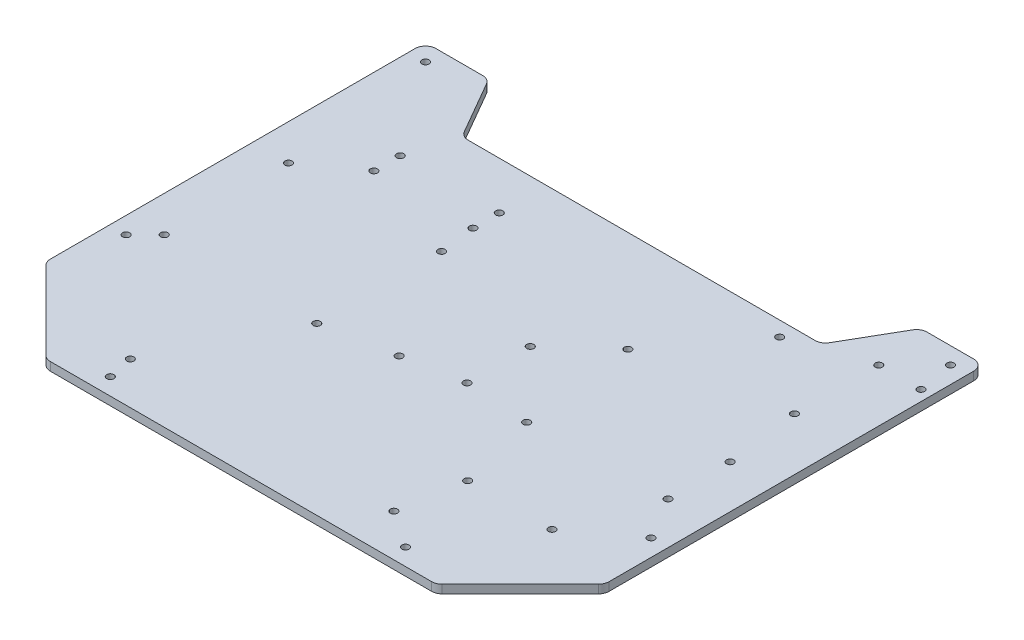
SolidWorks part; units mm, degrees
material "Acier non allié"
ref_plane "Front" through (0, 0, 0) normal (0, 0, 1) x (1, 0, 0)
ref_plane "Top" through (0, 0, 0) normal (0, 1, 0) x (1, 0, 0)
ref_plane "Right" through (0, 0, 0) normal (1, 0, 0) x (0, 0, -1)
sketch "Main scetch" plane through (0, 0, 0) normal (0, 1, 0) x (1, 0, 0)
  line L1 (0, 0) -> (132.5, 0) construction
  line L2 (0, 0) -> (0, 220) construction
  line L3 (0, 220) -> (132.5, 220) construction
  line L4 (132.5, 0) -> (132.5, 220) construction
  line L13 (-92.5, 0) -> (92.5, 0)
  line L14 (92.5, 0) -> (132.5, 40)
  line L15 (132.5, 40) -> (132.5, 220)
  line L16 (132.5, 220) -> (102.5, 220)
  line L17 (102.5, 220) -> (85.1795, 190)
  line L18 (85.1795, 190) -> (-85.1795, 190)
  line L19 (-102.5, 220) -> (-85.1795, 190)
  line L20 (-132.5, 220) -> (-102.5, 220)
  line L21 (-132.5, 40) -> (-132.5, 220)
  line L22 (-92.5, 0) -> (-132.5, 40)
  point P11 (0, 190)
  dimension "132.5" = 132.5
  dimension "D2" = 220
  dimension "D1" = 40
  dimension "D3" = 40
  dimension "D4" = 30
  dimension "D5" = 60
  dimension "D6" = 30
extrude "Main extrusion" add sketch "Main scetch" along normal blind 4
fillet "Congé1" radius 5 10 edges at (-132.5, 2, -40) (-92.5, 2, 0) (92.5, 2, 0) (132.5, 2, -40) (132.5, 2, -220) (102.5, 2, -220) (85.1795, 2, -190) (-85.1795, 2, -190) (-102.5, 2, -220) (-132.5, 2, -220)
sketch "Esquisse1" plane through (0, 4, 0) normal (0, 1, 0) x (1, 0, 0)
  line L0 (0, 0) -> (0, 218.5516) construction
  line L1 (132.5, 42.0711) -> (132.5, 215) construction
  line L2 (127.5, 220) -> (105.3868, 220) construction
  line L3 (-90.4289, 0) -> (90.4289, 0) construction
  circle A0 centre (70, 8) radius 1
  circle A1 centre (124.5, 70) radius 1
  circle A2 centre (124.5, 212) radius 1
  circle A3 centre (-124.5, 212) radius 1
  circle A4 centre (-124.5, 70) radius 1
  circle A5 centre (-70, 8) radius 1
  dimension "D1" = 2
  dimension "D2" = 2
  dimension "D3" = 2
  dimension "D4" = 8
  dimension "D5" = 8
  dimension "D6" = 8
  dimension "D7" = 8
  dimension "D8" = 70
  dimension "D9" = 70
extrude "Enlèv. mat.-Extru.1" cut sketch "Esquisse1" against normal through all
hole_wizard "Dégagement M31" positions "Esquisse2" profile "Esquisse3" hole size "M3" standard "ISO" end condition through all
sketch "Esquisse2" plane through (0, 4, 0) normal (0, 1, 0) x (1, 0, 0)
  point P0 (-124.5, 212)
  point P3 (-124.5, 70)
  point P6 (-70, 8)
  point P9 (70, 8)
  point P12 (124.5, 70)
  point P15 (124.5, 212)
sketch "Esquisse3" plane through (-124.5, 4, -212) normal (1, 0, 0) x (0, 0, 1)
  line L0 (0, 0) -> (0, 4)
  line L1 (0, 4) -> (1.7, 4)
  line L2 (1.7, 4) -> (1.7, 0)
  line L5 (1.7, 0) -> (0, 0)
  line L11 (0, -6.35) -> (0, 107.95) construction
  dimension "Diamètre du perçage jusqu'au prochain" = 3.4
  dimension "Profondeur du perçage jusqu'au prochain" = 4
sketch "Esquisse4" plane through (0, 4, 0) normal (0, 1, 0) x (1, 0, 0)
  line L0 (-132.5, 215) -> (-132.5, 42.0711) construction
  line L2 (82.2927, 190) -> (-82.2927, 190) construction
  line L3 (132.5, 42.0711) -> (132.5, 215) construction
  line L4 (-90.4289, 0) -> (90.4289, 0) construction
  line L5 (127.5, 220) -> (105.3868, 220) construction
  circle A1 centre (-68.5, 185) radius 1 construction
  circle A5 centre (72.5, 183) radius 1
  circle A6 centre (41.5, 142) radius 1
  circle A7 centre (107.5, 155) radius 1
  circle A8 centre (127.5, 195) radius 1
  circle A9 centre (112, 120) radius 1
  circle A10 centre (112.5, 90) radius 1
  circle A11 centre (17.2, 120) radius 1
  circle A12 centre (17.2, 90) radius 1
  circle A13 centre (47.5, 88) radius 1
  circle A14 centre (57.5, 50) radius 1
  circle A15 centre (97.5, 50) radius 1
  circle A16 centre (52.5, 20) radius 1
  circle A17 centre (-10, 85) radius 1
  circle A18 centre (-72.5, 20) radius 1
  circle A19 centre (107.5, 195) radius 1
  circle A23 centre (-115.5, 138) radius 1
  circle A24 centre (-42.86, 138) radius 1
  circle A25 centre (-115.5, 79.07) radius 1
  circle A26 centre (-42.8904, 78.82) radius 1
  circle A27 centre (-92, 167.5) radius 1
  circle A28 centre (-45, 167.5) radius 1
  circle A29 centre (-92, 155) radius 1
  circle A30 centre (-45, 155) radius 1
  dimension "D4" = 2
  dimension "D13" = 2
  dimension "D16" = 2
  dimension "D19" = 2
  dimension "D24" = 2
  dimension "D25" = 2
  dimension "D28" = 2
  dimension "D30" = 2
  dimension "D32" = 2
  dimension "D36" = 2
  dimension "D37" = 2
  dimension "D40" = 2
  dimension "D48" = 2
  dimension "D49" = 2
  dimension "D50" = 2
  dimension "D52" = 2
  dimension "D11" = 2
  dimension "D12" = 2
  dimension "D65" = 2
  dimension "D66" = 2
  dimension "D58" = 2
  dimension "D61" = 2
  dimension "D70" = 2
  dimension "D71" = 2
  dimension "D14" = 205
  dimension "D15" = 7
  dimension "D20" = 25
  dimension "D21" = 65
  dimension "D22" = 5
  dimension "D23" = 25
  dimension "D26" = 20.5
  dimension "D27" = 100
  dimension "D29" = 30
  dimension "D31" = 115.3
  dimension "D33" = 115.3
  dimension "D34" = 132
  dimension "D35" = 85
  dimension "D38" = 50
  dimension "D39" = 75
  dimension "D41" = 35
  dimension "D42" = 80
  dimension "D43" = 20
  dimension "D44" = 20
  dimension "D45" = 205
  dimension "D46" = 85
  dimension "D47" = 142.5
  dimension "D51" = 25
  dimension "D53" = 25
  dimension "D54" = 5
  dimension "D55" = 64
  dimension "D7" = 59.18
  dimension "D8" = 72.64
  dimension "D9" = 58.93
  dimension "D10" = 72.61
  dimension "D67" = 17
  dimension "D68" = 138
  dimension "D56" = 23.5
  dimension "D57" = 23.5
  dimension "D59" = 17.5
  dimension "D60" = 17.5
  dimension "D62" = 12.5
  dimension "D63" = 12.5
  dimension "D64" = 23.5
  dimension "D69" = 23.5
  dimension "D17" = 41
  dimension "D18" = 31
extrude "Enlèv. mat.-Extru.2" cut sketch "Esquisse4" against normal through all
hole_wizard "Dégagement M32" positions "Esquisse5" profile "Esquisse6" hole size "M3" standard "ISO" end condition through all
sketch "Esquisse5" plane through (0, 4, 0) normal (0, 1, 0) x (1, 0, 0)
  point P9 (17.2, 120)
  point P18 (41.5, 142)
  point P21 (72.5, 183)
  point P24 (107.5, 155)
  point P27 (127.5, 195)
  point P30 (112, 120)
  point P33 (112.5, 90)
  point P36 (47.5, 88)
  point P39 (17.2, 90)
  point P42 (57.5, 50)
  point P45 (97.5, 50)
  point P48 (-10, 85)
  point P51 (-72.5, 20)
  point P54 (52.5, 20)
  point P57 (107.5, 195)
  point P86 (-115.5, 138)
  point P89 (-42.86, 138)
  point P92 (-115.5, 79.07)
  point P95 (-42.8904, 78.82)
  point P102 (-92, 167.5)
  point P105 (-92, 155)
  point P108 (-45, 155)
  point P111 (-45, 167.5)
sketch "Esquisse6" plane through (17.2, 4, -120) normal (1, 0, 0) x (0, 0, 1)
  line L0 (0, 0) -> (0, 4)
  line L1 (0, 4) -> (1.7, 4)
  line L2 (1.7, 4) -> (1.7, 0)
  line L5 (1.7, 0) -> (0, 0)
  line L11 (0, -6.35) -> (0, 107.95) construction
  dimension "Diamètre du perçage jusqu'au prochain" = 3.4
  dimension "Profondeur du perçage jusqu'au prochain" = 4
equation "\"WIDTH\"= 300mm'Total width of the robot"
equation "\"LENGTH\"= 220mm'Total length of the robot"
equation "\"D2@Main scetch\" = \"LENGTH\""
equation "\"CUT_DEPTH\"= 45mm'Depth of the cut on the edges of the plate"
equation "\"Plate_th\"= 3mm'Thickness of the plate"
equation "\"D1\"= \"Plate_th\""
equation "\"D47@Esquisse4\"=(80+205)/2"
